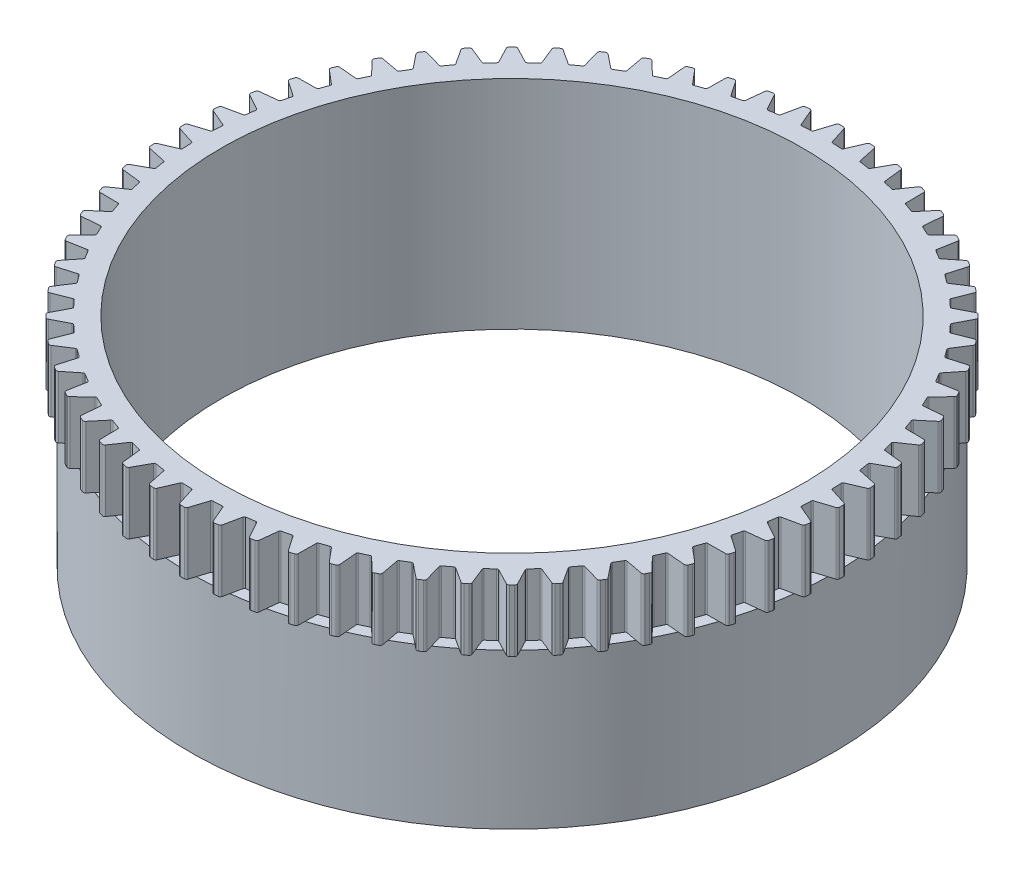
SolidWorks part; units mm, degrees
material "PET"
ref_plane "Front Plane" through (0, 0, 0) normal (0, 0, 1) x (1, 0, 0)
ref_plane "Top Plane" through (0, 0, 0) normal (0, 1, 0) x (1, 0, 0)
ref_plane "Right Plane" through (0, 0, 0) normal (1, 0, 0) x (0, 0, -1)
sketch "Sketch1" plane through (0, 0, 0) normal (0, 1, 0) x (1, 0, 0)
  line L0 (0, 53.7167) -> (0, -50.4595) construction
  line L1 (-0.5164, 42.2908) -> (-1.2072, 40.1152)
  line L2 (-0.2305, 42.5) -> (0.2305, 42.5)
  line L3 (0.5164, 42.2908) -> (1.2072, 40.1152)
  line L4 (3.6313, 42.1378) -> (2.7306, 40.0403)
  line L5 (4.6592, 42.0365) -> (5.1334, 39.8037)
  line L6 (3.9363, 42.3179) -> (4.3951, 42.2728)
  line L7 (7.744, 41.5789) -> (6.642, 39.5799)
  line L8 (8.757, 41.3774) -> (9.0101, 39.1088)
  line L9 (8.0653, 41.7283) -> (8.5174, 41.6384)
  line L10 (11.7822, 40.6197) -> (10.4896, 38.7383)
  line L11 (12.7706, 40.3199) -> (12.8001, 38.0374)
  line L12 (12.1165, 40.7369) -> (12.5577, 40.6031)
  line L13 (15.7069, 39.2692) -> (14.2361, 37.5236)
  line L14 (16.6611, 38.874) -> (16.4667, 36.5996)
  line L15 (16.0511, 39.3531) -> (16.477, 39.1767)
  line L16 (19.4803, 37.5406) -> (17.8455, 35.9475)
  line L17 (20.3912, 37.0537) -> (19.9748, 34.8093)
  line L18 (19.8311, 37.5903) -> (20.2376, 37.373)
  line L19 (23.0661, 35.4504) -> (21.283, 34.0252)
  line L20 (23.9249, 34.8766) -> (23.2906, 32.6838)
  line L21 (23.4201, 35.4655) -> (23.8034, 35.2094)
  line L22 (26.4298, 33.0188) -> (24.5156, 31.7753)
  line L23 (27.2282, 32.3636) -> (26.382, 30.2436)
  line L24 (26.7835, 32.9992) -> (27.1399, 32.7067)
  line L25 (29.5389, 30.2693) -> (27.5121, 29.2193)
  line L26 (30.2693, 29.5389) -> (29.2193, 27.5121)
  line L27 (29.8891, 30.215) -> (30.215, 29.8891)
  line L28 (32.3636, 27.2282) -> (30.2436, 26.382)
  line L29 (33.0188, 26.4298) -> (31.7753, 24.5156)
  line L30 (32.7067, 27.1399) -> (32.9992, 26.7835)
  line L31 (34.8766, 23.9249) -> (32.6838, 23.2906)
  line L32 (35.4504, 23.0661) -> (34.0252, 21.283)
  line L33 (35.2094, 23.8034) -> (35.4655, 23.4201)
  line L34 (37.0537, 20.3912) -> (34.8093, 19.9748)
  line L35 (37.5406, 19.4803) -> (35.9475, 17.8455)
  line L36 (37.373, 20.2376) -> (37.5903, 19.8311)
  line L37 (38.874, 16.6611) -> (36.5996, 16.4667)
  line L38 (39.2692, 15.7069) -> (37.5236, 14.2361)
  line L39 (39.1767, 16.477) -> (39.3531, 16.0511)
  line L40 (40.3199, 12.7706) -> (38.0374, 12.8001)
  line L41 (40.6197, 11.7822) -> (38.7383, 10.4896)
  line L42 (40.6031, 12.5577) -> (40.7369, 12.1165)
  line L43 (41.3774, 8.757) -> (39.1088, 9.0101)
  line L44 (41.5789, 7.744) -> (39.5799, 6.642)
  line L45 (41.6384, 8.5174) -> (41.7283, 8.0653)
  line L46 (42.0365, 4.6592) -> (39.8037, 5.1334)
  line L47 (42.1378, 3.6313) -> (40.0403, 2.7306)
  line L48 (42.2728, 4.3951) -> (42.3179, 3.9363)
  line L49 (42.2908, 0.5164) -> (40.1152, 1.2072)
  line L50 (42.2908, -0.5164) -> (40.1152, -1.2072)
  line L51 (42.5, 0.2305) -> (42.5, -0.2305)
  line L52 (42.1378, -3.6313) -> (40.0403, -2.7306)
  line L53 (42.0365, -4.6592) -> (39.8037, -5.1334)
  line L54 (42.3179, -3.9363) -> (42.2728, -4.3951)
  line L55 (41.5789, -7.744) -> (39.5799, -6.642)
  line L56 (41.3774, -8.757) -> (39.1088, -9.0101)
  line L57 (41.7283, -8.0653) -> (41.6384, -8.5174)
  line L58 (40.6197, -11.7822) -> (38.7383, -10.4896)
  line L59 (40.3199, -12.7706) -> (38.0374, -12.8001)
  line L60 (40.7369, -12.1165) -> (40.6031, -12.5577)
  line L61 (39.2692, -15.7069) -> (37.5236, -14.2361)
  line L62 (38.874, -16.6611) -> (36.5996, -16.4667)
  line L63 (39.3531, -16.0511) -> (39.1767, -16.477)
  line L64 (37.5406, -19.4803) -> (35.9475, -17.8455)
  line L65 (37.0537, -20.3912) -> (34.8093, -19.9748)
  line L66 (37.5903, -19.8311) -> (37.373, -20.2376)
  line L67 (35.4504, -23.0661) -> (34.0252, -21.283)
  line L68 (34.8766, -23.9249) -> (32.6838, -23.2906)
  line L69 (35.4655, -23.4201) -> (35.2094, -23.8034)
  line L70 (33.0188, -26.4298) -> (31.7753, -24.5156)
  line L71 (32.3636, -27.2282) -> (30.2436, -26.382)
  line L72 (32.9992, -26.7835) -> (32.7067, -27.1399)
  line L73 (30.2693, -29.5389) -> (29.2193, -27.5121)
  line L74 (29.5389, -30.2693) -> (27.5121, -29.2193)
  line L75 (30.215, -29.8891) -> (29.8891, -30.215)
  line L76 (27.2282, -32.3636) -> (26.382, -30.2436)
  line L77 (26.4298, -33.0188) -> (24.5156, -31.7753)
  line L78 (27.1399, -32.7067) -> (26.7835, -32.9992)
  line L79 (23.9249, -34.8766) -> (23.2906, -32.6838)
  line L80 (23.0661, -35.4504) -> (21.283, -34.0252)
  line L81 (23.8034, -35.2094) -> (23.4201, -35.4655)
  line L82 (20.3912, -37.0537) -> (19.9748, -34.8093)
  line L83 (19.4803, -37.5406) -> (17.8455, -35.9475)
  line L84 (20.2376, -37.373) -> (19.8311, -37.5903)
  line L85 (16.6611, -38.874) -> (16.4667, -36.5996)
  line L86 (15.7069, -39.2692) -> (14.2361, -37.5236)
  line L87 (16.477, -39.1767) -> (16.0511, -39.3531)
  line L88 (12.7706, -40.3199) -> (12.8001, -38.0374)
  line L89 (11.7822, -40.6197) -> (10.4896, -38.7383)
  line L90 (12.5577, -40.6031) -> (12.1165, -40.7369)
  line L91 (8.757, -41.3774) -> (9.0101, -39.1088)
  line L92 (7.744, -41.5789) -> (6.642, -39.5799)
  line L93 (8.5174, -41.6384) -> (8.0653, -41.7283)
  line L94 (4.6592, -42.0365) -> (5.1334, -39.8037)
  line L95 (3.6313, -42.1378) -> (2.7306, -40.0403)
  line L96 (4.3951, -42.2728) -> (3.9363, -42.3179)
  line L97 (0.5164, -42.2908) -> (1.2072, -40.1152)
  line L98 (-0.5164, -42.2908) -> (-1.2072, -40.1152)
  line L99 (0.2305, -42.5) -> (-0.2305, -42.5)
  line L100 (-3.6313, -42.1378) -> (-2.7306, -40.0403)
  line L101 (-4.6592, -42.0365) -> (-5.1334, -39.8037)
  line L102 (-3.9363, -42.3179) -> (-4.3951, -42.2728)
  line L103 (-7.744, -41.5789) -> (-6.642, -39.5799)
  line L104 (-8.757, -41.3774) -> (-9.0101, -39.1088)
  line L105 (-8.0653, -41.7283) -> (-8.5174, -41.6384)
  line L106 (-11.7822, -40.6197) -> (-10.4896, -38.7383)
  line L107 (-12.7706, -40.3199) -> (-12.8001, -38.0374)
  line L108 (-12.1165, -40.7369) -> (-12.5577, -40.6031)
  line L109 (-15.7069, -39.2692) -> (-14.2361, -37.5236)
  line L110 (-16.6611, -38.874) -> (-16.4667, -36.5996)
  line L111 (-16.0511, -39.3531) -> (-16.477, -39.1767)
  line L112 (-19.4803, -37.5406) -> (-17.8455, -35.9475)
  line L113 (-20.3912, -37.0537) -> (-19.9748, -34.8093)
  line L114 (-19.8311, -37.5903) -> (-20.2376, -37.373)
  line L115 (-23.0661, -35.4504) -> (-21.283, -34.0252)
  line L116 (-23.9249, -34.8766) -> (-23.2906, -32.6838)
  line L117 (-23.4201, -35.4655) -> (-23.8034, -35.2094)
  line L118 (-26.4298, -33.0188) -> (-24.5156, -31.7753)
  line L119 (-27.2282, -32.3636) -> (-26.382, -30.2436)
  line L120 (-26.7835, -32.9992) -> (-27.1399, -32.7067)
  line L121 (-29.5389, -30.2693) -> (-27.5121, -29.2193)
  line L122 (-30.2693, -29.5389) -> (-29.2193, -27.5121)
  line L123 (-29.8891, -30.215) -> (-30.215, -29.8891)
  line L124 (-32.3636, -27.2282) -> (-30.2436, -26.382)
  line L125 (-33.0188, -26.4298) -> (-31.7753, -24.5156)
  line L126 (-32.7067, -27.1399) -> (-32.9992, -26.7835)
  line L127 (-34.8766, -23.9249) -> (-32.6838, -23.2906)
  line L128 (-35.4504, -23.0661) -> (-34.0252, -21.283)
  line L129 (-35.2094, -23.8034) -> (-35.4655, -23.4201)
  line L130 (-37.0537, -20.3912) -> (-34.8093, -19.9748)
  line L131 (-37.5406, -19.4803) -> (-35.9475, -17.8455)
  line L132 (-37.373, -20.2376) -> (-37.5903, -19.8311)
  line L133 (-38.874, -16.6611) -> (-36.5996, -16.4667)
  line L134 (-39.2692, -15.7069) -> (-37.5236, -14.2361)
  line L135 (-39.1767, -16.477) -> (-39.3531, -16.0511)
  line L136 (-40.3199, -12.7706) -> (-38.0374, -12.8001)
  line L137 (-40.6197, -11.7822) -> (-38.7383, -10.4896)
  line L138 (-40.6031, -12.5577) -> (-40.7369, -12.1165)
  line L139 (-41.3774, -8.757) -> (-39.1088, -9.0101)
  line L140 (-41.5789, -7.744) -> (-39.5799, -6.642)
  line L141 (-41.6384, -8.5174) -> (-41.7283, -8.0653)
  line L142 (-42.0365, -4.6592) -> (-39.8037, -5.1334)
  line L143 (-42.1378, -3.6313) -> (-40.0403, -2.7306)
  line L144 (-42.2728, -4.3951) -> (-42.3179, -3.9363)
  line L145 (-42.2908, -0.5164) -> (-40.1152, -1.2072)
  line L146 (-42.2908, 0.5164) -> (-40.1152, 1.2072)
  line L147 (-42.5, -0.2305) -> (-42.5, 0.2305)
  line L148 (-42.1378, 3.6313) -> (-40.0403, 2.7306)
  line L149 (-42.0365, 4.6592) -> (-39.8037, 5.1334)
  line L150 (-42.3179, 3.9363) -> (-42.2728, 4.3951)
  line L151 (-41.5789, 7.744) -> (-39.5799, 6.642)
  line L152 (-41.3774, 8.757) -> (-39.1088, 9.0101)
  line L153 (-41.7283, 8.0653) -> (-41.6384, 8.5174)
  line L154 (-40.6197, 11.7822) -> (-38.7383, 10.4896)
  line L155 (-40.3199, 12.7706) -> (-38.0374, 12.8001)
  line L156 (-40.7369, 12.1165) -> (-40.6031, 12.5577)
  line L157 (-39.2692, 15.7069) -> (-37.5236, 14.2361)
  line L158 (-38.874, 16.6611) -> (-36.5996, 16.4667)
  line L159 (-39.3531, 16.0511) -> (-39.1767, 16.477)
  line L160 (-37.5406, 19.4803) -> (-35.9475, 17.8455)
  line L161 (-37.0537, 20.3912) -> (-34.8093, 19.9748)
  line L162 (-37.5903, 19.8311) -> (-37.373, 20.2376)
  line L163 (-35.4504, 23.0661) -> (-34.0252, 21.283)
  line L164 (-34.8766, 23.9249) -> (-32.6838, 23.2906)
  line L165 (-35.4655, 23.4201) -> (-35.2094, 23.8034)
  line L166 (-33.0188, 26.4298) -> (-31.7753, 24.5156)
  line L167 (-32.3636, 27.2282) -> (-30.2436, 26.382)
  line L168 (-32.9992, 26.7835) -> (-32.7067, 27.1399)
  line L169 (-30.2693, 29.5389) -> (-29.2193, 27.5121)
  line L170 (-29.5389, 30.2693) -> (-27.5121, 29.2193)
  line L171 (-30.215, 29.8891) -> (-29.8891, 30.215)
  line L172 (-27.2282, 32.3636) -> (-26.382, 30.2436)
  line L173 (-26.4298, 33.0188) -> (-24.5156, 31.7753)
  line L174 (-27.1399, 32.7067) -> (-26.7835, 32.9992)
  line L175 (-23.9249, 34.8766) -> (-23.2906, 32.6838)
  line L176 (-23.0661, 35.4504) -> (-21.283, 34.0252)
  line L177 (-23.8034, 35.2094) -> (-23.4201, 35.4655)
  line L178 (-20.3912, 37.0537) -> (-19.9748, 34.8093)
  line L179 (-19.4803, 37.5406) -> (-17.8455, 35.9475)
  line L180 (-20.2376, 37.373) -> (-19.8311, 37.5903)
  line L181 (-16.6611, 38.874) -> (-16.4667, 36.5996)
  line L182 (-15.7069, 39.2692) -> (-14.2361, 37.5236)
  line L183 (-16.477, 39.1767) -> (-16.0511, 39.3531)
  line L184 (-12.7706, 40.3199) -> (-12.8001, 38.0374)
  line L185 (-11.7822, 40.6197) -> (-10.4896, 38.7383)
  line L186 (-12.5577, 40.6031) -> (-12.1165, 40.7369)
  line L187 (-8.757, 41.3774) -> (-9.0101, 39.1088)
  line L188 (-7.744, 41.5789) -> (-6.642, 39.5799)
  line L189 (-8.5174, 41.6384) -> (-8.0653, 41.7283)
  line L190 (-4.6592, 42.0365) -> (-5.1334, 39.8037)
  line L191 (-3.6313, 42.1378) -> (-2.7306, 40.0403)
  line L192 (-4.3951, 42.2728) -> (-3.9363, 42.3179)
  arc A0 (-1.3909, 39.9758) -> (-2.5341, 39.9196) centre (0, 0) ccw
  arc A1 (-0.5164, 42.2908) -> (-0.2305, 42.5) centre (-0.2305, 42.2) cw
  arc A2 (0.2305, 42.5) -> (0.5164, 42.2908) centre (0.2305, 42.2) cw
  arc A3 (1.2072, 40.1152) -> (1.3909, 39.9758) centre (1.3979, 40.1757) ccw
  arc A4 (-1.2072, 40.1152) -> (-1.3909, 39.9758) centre (-1.3979, 40.1757) cw
  arc A5 (2.7306, 40.0403) -> (2.5341, 39.9196) centre (2.5468, 40.1192) cw
  arc A6 (5.1334, 39.8037) -> (5.3025, 39.647) centre (5.329, 39.8452) ccw
  arc A7 (4.3951, 42.2728) -> (4.6592, 42.0365) centre (4.3657, 41.9742) cw
  arc A8 (3.6313, 42.1378) -> (3.9363, 42.3179) centre (3.9069, 42.0194) cw
  arc A9 (6.642, 39.5799) -> (6.4347, 39.479) centre (6.4669, 39.6764) cw
  arc A10 (9.0101, 39.1088) -> (9.1631, 38.9363) centre (9.2089, 39.131) ccw
  arc A11 (8.5174, 41.6384) -> (8.757, 41.3774) centre (8.4589, 41.3442) cw
  arc A12 (7.744, 41.5789) -> (8.0653, 41.7283) centre (8.0067, 41.4341) cw
  arc A13 (10.4896, 38.7383) -> (10.2734, 38.6582) centre (10.3247, 38.8515) cw
  arc A14 (12.8001, 38.0374) -> (12.9354, 37.8507) centre (13, 38.04) ccw
  arc A15 (12.5577, 40.6031) -> (12.7706, 40.3199) centre (12.4706, 40.316) cw
  arc A16 (11.7822, 40.6197) -> (12.1165, 40.7369) centre (12.0294, 40.4498) cw
  arc A17 (14.2361, 37.5236) -> (14.0131, 37.4651) centre (14.0831, 37.6524) cw
  arc A18 (16.4667, 36.5996) -> (16.5831, 36.4006) centre (16.666, 36.5826) ccw
  arc A19 (16.477, 39.1767) -> (16.6611, 38.874) centre (16.3622, 38.8995) cw
  arc A20 (15.7069, 39.2692) -> (16.0511, 39.3531) centre (15.9363, 39.0759) cw
  arc A21 (17.8455, 35.9475) -> (17.6178, 35.9112) centre (17.7059, 36.0907) cw
  arc A22 (19.9748, 34.8093) -> (20.0711, 34.5999) centre (20.1715, 34.7729) ccw
  arc A23 (20.2376, 37.373) -> (20.3912, 37.0537) centre (20.0962, 37.1084) cw
  arc A24 (19.4803, 37.5406) -> (19.8311, 37.5903) centre (19.6897, 37.3257) cw
  arc A25 (21.283, 34.0252) -> (21.0529, 34.0114) centre (21.1581, 34.1815) cw
  arc A26 (23.2906, 32.6838) -> (23.3659, 32.4659) centre (23.4827, 32.6283) ccw
  arc A27 (23.8034, 35.2094) -> (23.9249, 34.8766) centre (23.6367, 34.96) cw
  arc A28 (23.0661, 35.4504) -> (23.4201, 35.4655) centre (23.2534, 35.2161) cw
  arc A29 (24.5156, 31.7753) -> (24.2852, 31.7841) centre (24.4066, 31.943) cw
  arc A30 (26.382, 30.2436) -> (26.4356, 30.0193) centre (26.5677, 30.1694) ccw
  arc A31 (27.1399, 32.7067) -> (27.2282, 32.3636) centre (26.9496, 32.4748) cw
  arc A32 (26.4298, 33.0188) -> (26.7835, 32.9992) centre (26.5932, 32.7673) cw
  arc A33 (27.5121, 29.2193) -> (27.2837, 29.2507) centre (27.4201, 29.3969) cw
  arc A34 (29.2193, 27.5121) -> (29.2507, 27.2837) centre (29.3969, 27.4201) ccw
  arc A35 (30.215, 29.8891) -> (30.2693, 29.5389) centre (30.0029, 29.6769) cw
  arc A36 (29.5389, 30.2693) -> (29.8891, 30.215) centre (29.6769, 30.0029) cw
  arc A37 (30.2436, 26.382) -> (30.0193, 26.4356) centre (30.1694, 26.5677) cw
  arc A38 (31.7753, 24.5156) -> (31.7841, 24.2852) centre (31.943, 24.4066) ccw
  arc A39 (32.9992, 26.7835) -> (33.0188, 26.4298) centre (32.7673, 26.5932) cw
  arc A40 (32.3636, 27.2282) -> (32.7067, 27.1399) centre (32.4748, 26.9496) cw
  arc A41 (32.6838, 23.2906) -> (32.4659, 23.3659) centre (32.6283, 23.4827) cw
  arc A42 (34.0252, 21.283) -> (34.0114, 21.0529) centre (34.1815, 21.1581) ccw
  arc A43 (35.4655, 23.4201) -> (35.4504, 23.0661) centre (35.2161, 23.2534) cw
  arc A44 (34.8766, 23.9249) -> (35.2094, 23.8034) centre (34.96, 23.6367) cw
  arc A45 (34.8093, 19.9748) -> (34.5999, 20.0711) centre (34.7729, 20.1715) cw
  arc A46 (35.9475, 17.8455) -> (35.9112, 17.6178) centre (36.0907, 17.7059) ccw
  arc A47 (37.5903, 19.8311) -> (37.5406, 19.4803) centre (37.3257, 19.6897) cw
  arc A48 (37.0537, 20.3912) -> (37.373, 20.2376) centre (37.1084, 20.0962) cw
  arc A49 (36.5996, 16.4667) -> (36.4006, 16.5831) centre (36.5826, 16.666) cw
  arc A50 (37.5236, 14.2361) -> (37.4651, 14.0131) centre (37.6524, 14.0831) ccw
  arc A51 (39.3531, 16.0511) -> (39.2692, 15.7069) centre (39.0759, 15.9363) cw
  arc A52 (38.874, 16.6611) -> (39.1767, 16.477) centre (38.8995, 16.3622) cw
  arc A53 (38.0374, 12.8001) -> (37.8507, 12.9354) centre (38.04, 13) cw
  arc A54 (38.7383, 10.4896) -> (38.6582, 10.2734) centre (38.8515, 10.3247) ccw
  arc A55 (40.7369, 12.1165) -> (40.6197, 11.7822) centre (40.4498, 12.0294) cw
  arc A56 (40.3199, 12.7706) -> (40.6031, 12.5577) centre (40.316, 12.4706) cw
  arc A57 (39.1088, 9.0101) -> (38.9363, 9.1631) centre (39.131, 9.2089) cw
  arc A58 (39.5799, 6.642) -> (39.479, 6.4347) centre (39.6764, 6.4669) ccw
  arc A59 (41.7283, 8.0653) -> (41.5789, 7.744) centre (41.4341, 8.0067) cw
  arc A60 (41.3774, 8.757) -> (41.6384, 8.5174) centre (41.3442, 8.4589) cw
  arc A61 (39.8037, 5.1334) -> (39.647, 5.3025) centre (39.8452, 5.329) cw
  arc A62 (40.0403, 2.7306) -> (39.9196, 2.5341) centre (40.1192, 2.5468) ccw
  arc A63 (42.3179, 3.9363) -> (42.1378, 3.6313) centre (42.0194, 3.9069) cw
  arc A64 (42.0365, 4.6592) -> (42.2728, 4.3951) centre (41.9742, 4.3657) cw
  arc A65 (40.1152, 1.2072) -> (39.9758, 1.3909) centre (40.1757, 1.3979) cw
  arc A66 (40.1152, -1.2072) -> (39.9758, -1.3909) centre (40.1757, -1.3979) ccw
  arc A67 (42.5, -0.2305) -> (42.2908, -0.5164) centre (42.2, -0.2305) cw
  arc A68 (42.2908, 0.5164) -> (42.5, 0.2305) centre (42.2, 0.2305) cw
  arc A69 (40.0403, -2.7306) -> (39.9196, -2.5341) centre (40.1192, -2.5468) cw
  arc A70 (39.8037, -5.1334) -> (39.647, -5.3025) centre (39.8452, -5.329) ccw
  arc A71 (42.2728, -4.3951) -> (42.0365, -4.6592) centre (41.9742, -4.3657) cw
  arc A72 (42.1378, -3.6313) -> (42.3179, -3.9363) centre (42.0194, -3.9069) cw
  arc A73 (39.5799, -6.642) -> (39.479, -6.4347) centre (39.6764, -6.4669) cw
  arc A74 (39.1088, -9.0101) -> (38.9363, -9.1631) centre (39.131, -9.2089) ccw
  arc A75 (41.6384, -8.5174) -> (41.3774, -8.757) centre (41.3442, -8.4589) cw
  arc A76 (41.5789, -7.744) -> (41.7283, -8.0653) centre (41.4341, -8.0067) cw
  arc A77 (38.7383, -10.4896) -> (38.6582, -10.2734) centre (38.8515, -10.3247) cw
  arc A78 (38.0374, -12.8001) -> (37.8507, -12.9354) centre (38.04, -13) ccw
  arc A79 (40.6031, -12.5577) -> (40.3199, -12.7706) centre (40.316, -12.4706) cw
  arc A80 (40.6197, -11.7822) -> (40.7369, -12.1165) centre (40.4498, -12.0294) cw
  arc A81 (37.5236, -14.2361) -> (37.4651, -14.0131) centre (37.6524, -14.0831) cw
  arc A82 (36.5996, -16.4667) -> (36.4006, -16.5831) centre (36.5826, -16.666) ccw
  arc A83 (39.1767, -16.477) -> (38.874, -16.6611) centre (38.8995, -16.3622) cw
  arc A84 (39.2692, -15.7069) -> (39.3531, -16.0511) centre (39.0759, -15.9363) cw
  arc A85 (35.9475, -17.8455) -> (35.9112, -17.6178) centre (36.0907, -17.7059) cw
  arc A86 (34.8093, -19.9748) -> (34.5999, -20.0711) centre (34.7729, -20.1715) ccw
  arc A87 (37.373, -20.2376) -> (37.0537, -20.3912) centre (37.1084, -20.0962) cw
  arc A88 (37.5406, -19.4803) -> (37.5903, -19.8311) centre (37.3257, -19.6897) cw
  arc A89 (34.0252, -21.283) -> (34.0114, -21.0529) centre (34.1815, -21.1581) cw
  arc A90 (32.6838, -23.2906) -> (32.4659, -23.3659) centre (32.6283, -23.4827) ccw
  arc A91 (35.2094, -23.8034) -> (34.8766, -23.9249) centre (34.96, -23.6367) cw
  arc A92 (35.4504, -23.0661) -> (35.4655, -23.4201) centre (35.2161, -23.2534) cw
  arc A93 (31.7753, -24.5156) -> (31.7841, -24.2852) centre (31.943, -24.4066) cw
  arc A94 (30.2436, -26.382) -> (30.0193, -26.4356) centre (30.1694, -26.5677) ccw
  arc A95 (32.7067, -27.1399) -> (32.3636, -27.2282) centre (32.4748, -26.9496) cw
  arc A96 (33.0188, -26.4298) -> (32.9992, -26.7835) centre (32.7673, -26.5932) cw
  arc A97 (29.2193, -27.5121) -> (29.2507, -27.2837) centre (29.3969, -27.4201) cw
  arc A98 (27.5121, -29.2193) -> (27.2837, -29.2507) centre (27.4201, -29.3969) ccw
  arc A99 (29.8891, -30.215) -> (29.5389, -30.2693) centre (29.6769, -30.0029) cw
  arc A100 (30.2693, -29.5389) -> (30.215, -29.8891) centre (30.0029, -29.6769) cw
  arc A101 (26.382, -30.2436) -> (26.4356, -30.0193) centre (26.5677, -30.1694) cw
  arc A102 (24.5156, -31.7753) -> (24.2852, -31.7841) centre (24.4066, -31.943) ccw
  arc A103 (26.7835, -32.9992) -> (26.4298, -33.0188) centre (26.5932, -32.7673) cw
  arc A104 (27.2282, -32.3636) -> (27.1399, -32.7067) centre (26.9496, -32.4748) cw
  arc A105 (23.2906, -32.6838) -> (23.3659, -32.4659) centre (23.4827, -32.6283) cw
  arc A106 (21.283, -34.0252) -> (21.0529, -34.0114) centre (21.1581, -34.1815) ccw
  arc A107 (23.4201, -35.4655) -> (23.0661, -35.4504) centre (23.2534, -35.2161) cw
  arc A108 (23.9249, -34.8766) -> (23.8034, -35.2094) centre (23.6367, -34.96) cw
  arc A109 (19.9748, -34.8093) -> (20.0711, -34.5999) centre (20.1715, -34.7729) cw
  arc A110 (17.8455, -35.9475) -> (17.6178, -35.9112) centre (17.7059, -36.0907) ccw
  arc A111 (19.8311, -37.5903) -> (19.4803, -37.5406) centre (19.6897, -37.3257) cw
  arc A112 (20.3912, -37.0537) -> (20.2376, -37.373) centre (20.0962, -37.1084) cw
  arc A113 (16.4667, -36.5996) -> (16.5831, -36.4006) centre (16.666, -36.5826) cw
  arc A114 (14.2361, -37.5236) -> (14.0131, -37.4651) centre (14.0831, -37.6524) ccw
  arc A115 (16.0511, -39.3531) -> (15.7069, -39.2692) centre (15.9363, -39.0759) cw
  arc A116 (16.6611, -38.874) -> (16.477, -39.1767) centre (16.3622, -38.8995) cw
  arc A117 (12.8001, -38.0374) -> (12.9354, -37.8507) centre (13, -38.04) cw
  arc A118 (10.4896, -38.7383) -> (10.2734, -38.6582) centre (10.3247, -38.8515) ccw
  arc A119 (12.1165, -40.7369) -> (11.7822, -40.6197) centre (12.0294, -40.4498) cw
  arc A120 (12.7706, -40.3199) -> (12.5577, -40.6031) centre (12.4706, -40.316) cw
  arc A121 (9.0101, -39.1088) -> (9.1631, -38.9363) centre (9.2089, -39.131) cw
  arc A122 (6.642, -39.5799) -> (6.4347, -39.479) centre (6.4669, -39.6764) ccw
  arc A123 (8.0653, -41.7283) -> (7.744, -41.5789) centre (8.0067, -41.4341) cw
  arc A124 (8.757, -41.3774) -> (8.5174, -41.6384) centre (8.4589, -41.3442) cw
  arc A125 (5.1334, -39.8037) -> (5.3025, -39.647) centre (5.329, -39.8452) cw
  arc A126 (2.7306, -40.0403) -> (2.5341, -39.9196) centre (2.5468, -40.1192) ccw
  arc A127 (3.9363, -42.3179) -> (3.6313, -42.1378) centre (3.9069, -42.0194) cw
  arc A128 (4.6592, -42.0365) -> (4.3951, -42.2728) centre (4.3657, -41.9742) cw
  arc A129 (1.2072, -40.1152) -> (1.3909, -39.9758) centre (1.3979, -40.1757) cw
  arc A130 (-1.2072, -40.1152) -> (-1.3909, -39.9758) centre (-1.3979, -40.1757) ccw
  arc A131 (-0.2305, -42.5) -> (-0.5164, -42.2908) centre (-0.2305, -42.2) cw
  arc A132 (0.5164, -42.2908) -> (0.2305, -42.5) centre (0.2305, -42.2) cw
  arc A133 (-2.7306, -40.0403) -> (-2.5341, -39.9196) centre (-2.5468, -40.1192) cw
  arc A134 (-5.1334, -39.8037) -> (-5.3025, -39.647) centre (-5.329, -39.8452) ccw
  arc A135 (-4.3951, -42.2728) -> (-4.6592, -42.0365) centre (-4.3657, -41.9742) cw
  arc A136 (-3.6313, -42.1378) -> (-3.9363, -42.3179) centre (-3.9069, -42.0194) cw
  arc A137 (-6.642, -39.5799) -> (-6.4347, -39.479) centre (-6.4669, -39.6764) cw
  arc A138 (-9.0101, -39.1088) -> (-9.1631, -38.9363) centre (-9.2089, -39.131) ccw
  arc A139 (-8.5174, -41.6384) -> (-8.757, -41.3774) centre (-8.4589, -41.3442) cw
  arc A140 (-7.744, -41.5789) -> (-8.0653, -41.7283) centre (-8.0067, -41.4341) cw
  arc A141 (-10.4896, -38.7383) -> (-10.2734, -38.6582) centre (-10.3247, -38.8515) cw
  arc A142 (-12.8001, -38.0374) -> (-12.9354, -37.8507) centre (-13, -38.04) ccw
  arc A143 (-12.5577, -40.6031) -> (-12.7706, -40.3199) centre (-12.4706, -40.316) cw
  arc A144 (-11.7822, -40.6197) -> (-12.1165, -40.7369) centre (-12.0294, -40.4498) cw
  arc A145 (-14.2361, -37.5236) -> (-14.0131, -37.4651) centre (-14.0831, -37.6524) cw
  arc A146 (-16.4667, -36.5996) -> (-16.5831, -36.4006) centre (-16.666, -36.5826) ccw
  arc A147 (-16.477, -39.1767) -> (-16.6611, -38.874) centre (-16.3622, -38.8995) cw
  arc A148 (-15.7069, -39.2692) -> (-16.0511, -39.3531) centre (-15.9363, -39.0759) cw
  arc A149 (-17.8455, -35.9475) -> (-17.6178, -35.9112) centre (-17.7059, -36.0907) cw
  arc A150 (-19.9748, -34.8093) -> (-20.0711, -34.5999) centre (-20.1715, -34.7729) ccw
  arc A151 (-20.2376, -37.373) -> (-20.3912, -37.0537) centre (-20.0962, -37.1084) cw
  arc A152 (-19.4803, -37.5406) -> (-19.8311, -37.5903) centre (-19.6897, -37.3257) cw
  arc A153 (-21.283, -34.0252) -> (-21.0529, -34.0114) centre (-21.1581, -34.1815) cw
  arc A154 (-23.2906, -32.6838) -> (-23.3659, -32.4659) centre (-23.4827, -32.6283) ccw
  arc A155 (-23.8034, -35.2094) -> (-23.9249, -34.8766) centre (-23.6367, -34.96) cw
  arc A156 (-23.0661, -35.4504) -> (-23.4201, -35.4655) centre (-23.2534, -35.2161) cw
  arc A157 (-24.5156, -31.7753) -> (-24.2852, -31.7841) centre (-24.4066, -31.943) cw
  arc A158 (-26.382, -30.2436) -> (-26.4356, -30.0193) centre (-26.5677, -30.1694) ccw
  arc A159 (-27.1399, -32.7067) -> (-27.2282, -32.3636) centre (-26.9496, -32.4748) cw
  arc A160 (-26.4298, -33.0188) -> (-26.7835, -32.9992) centre (-26.5932, -32.7673) cw
  arc A161 (-27.5121, -29.2193) -> (-27.2837, -29.2507) centre (-27.4201, -29.3969) cw
  arc A162 (-29.2193, -27.5121) -> (-29.2507, -27.2837) centre (-29.3969, -27.4201) ccw
  arc A163 (-30.215, -29.8891) -> (-30.2693, -29.5389) centre (-30.0029, -29.6769) cw
  arc A164 (-29.5389, -30.2693) -> (-29.8891, -30.215) centre (-29.6769, -30.0029) cw
  arc A165 (-30.2436, -26.382) -> (-30.0193, -26.4356) centre (-30.1694, -26.5677) cw
  arc A166 (-31.7753, -24.5156) -> (-31.7841, -24.2852) centre (-31.943, -24.4066) ccw
  arc A167 (-32.9992, -26.7835) -> (-33.0188, -26.4298) centre (-32.7673, -26.5932) cw
  arc A168 (-32.3636, -27.2282) -> (-32.7067, -27.1399) centre (-32.4748, -26.9496) cw
  arc A169 (-32.6838, -23.2906) -> (-32.4659, -23.3659) centre (-32.6283, -23.4827) cw
  arc A170 (-34.0252, -21.283) -> (-34.0114, -21.0529) centre (-34.1815, -21.1581) ccw
  arc A171 (-35.4655, -23.4201) -> (-35.4504, -23.0661) centre (-35.2161, -23.2534) cw
  arc A172 (-34.8766, -23.9249) -> (-35.2094, -23.8034) centre (-34.96, -23.6367) cw
  arc A173 (-34.8093, -19.9748) -> (-34.5999, -20.0711) centre (-34.7729, -20.1715) cw
  arc A174 (-35.9475, -17.8455) -> (-35.9112, -17.6178) centre (-36.0907, -17.7059) ccw
  arc A175 (-37.5903, -19.8311) -> (-37.5406, -19.4803) centre (-37.3257, -19.6897) cw
  arc A176 (-37.0537, -20.3912) -> (-37.373, -20.2376) centre (-37.1084, -20.0962) cw
  arc A177 (-36.5996, -16.4667) -> (-36.4006, -16.5831) centre (-36.5826, -16.666) cw
  arc A178 (-37.5236, -14.2361) -> (-37.4651, -14.0131) centre (-37.6524, -14.0831) ccw
  arc A179 (-39.3531, -16.0511) -> (-39.2692, -15.7069) centre (-39.0759, -15.9363) cw
  arc A180 (-38.874, -16.6611) -> (-39.1767, -16.477) centre (-38.8995, -16.3622) cw
  arc A181 (-38.0374, -12.8001) -> (-37.8507, -12.9354) centre (-38.04, -13) cw
  arc A182 (-38.7383, -10.4896) -> (-38.6582, -10.2734) centre (-38.8515, -10.3247) ccw
  arc A183 (-40.7369, -12.1165) -> (-40.6197, -11.7822) centre (-40.4498, -12.0294) cw
  arc A184 (-40.3199, -12.7706) -> (-40.6031, -12.5577) centre (-40.316, -12.4706) cw
  arc A185 (-39.1088, -9.0101) -> (-38.9363, -9.1631) centre (-39.131, -9.2089) cw
  arc A186 (-39.5799, -6.642) -> (-39.479, -6.4347) centre (-39.6764, -6.4669) ccw
  arc A187 (-41.7283, -8.0653) -> (-41.5789, -7.744) centre (-41.4341, -8.0067) cw
  arc A188 (-41.3774, -8.757) -> (-41.6384, -8.5174) centre (-41.3442, -8.4589) cw
  arc A189 (-39.8037, -5.1334) -> (-39.647, -5.3025) centre (-39.8452, -5.329) cw
  arc A190 (-40.0403, -2.7306) -> (-39.9196, -2.5341) centre (-40.1192, -2.5468) ccw
  arc A191 (-42.3179, -3.9363) -> (-42.1378, -3.6313) centre (-42.0194, -3.9069) cw
  arc A192 (-42.0365, -4.6592) -> (-42.2728, -4.3951) centre (-41.9742, -4.3657) cw
  arc A193 (-40.1152, -1.2072) -> (-39.9758, -1.3909) centre (-40.1757, -1.3979) cw
  arc A194 (-40.1152, 1.2072) -> (-39.9758, 1.3909) centre (-40.1757, 1.3979) ccw
  arc A195 (-42.5, 0.2305) -> (-42.2908, 0.5164) centre (-42.2, 0.2305) cw
  arc A196 (-42.2908, -0.5164) -> (-42.5, -0.2305) centre (-42.2, -0.2305) cw
  arc A197 (-40.0403, 2.7306) -> (-39.9196, 2.5341) centre (-40.1192, 2.5468) cw
  arc A198 (-39.8037, 5.1334) -> (-39.647, 5.3025) centre (-39.8452, 5.329) ccw
  arc A199 (-42.2728, 4.3951) -> (-42.0365, 4.6592) centre (-41.9742, 4.3657) cw
  arc A200 (-42.1378, 3.6313) -> (-42.3179, 3.9363) centre (-42.0194, 3.9069) cw
  arc A201 (-39.5799, 6.642) -> (-39.479, 6.4347) centre (-39.6764, 6.4669) cw
  arc A202 (-39.1088, 9.0101) -> (-38.9363, 9.1631) centre (-39.131, 9.2089) ccw
  arc A203 (-41.6384, 8.5174) -> (-41.3774, 8.757) centre (-41.3442, 8.4589) cw
  arc A204 (-41.5789, 7.744) -> (-41.7283, 8.0653) centre (-41.4341, 8.0067) cw
  arc A205 (-38.7383, 10.4896) -> (-38.6582, 10.2734) centre (-38.8515, 10.3247) cw
  arc A206 (-38.0374, 12.8001) -> (-37.8507, 12.9354) centre (-38.04, 13) ccw
  arc A207 (-40.6031, 12.5577) -> (-40.3199, 12.7706) centre (-40.316, 12.4706) cw
  arc A208 (-40.6197, 11.7822) -> (-40.7369, 12.1165) centre (-40.4498, 12.0294) cw
  arc A209 (-37.5236, 14.2361) -> (-37.4651, 14.0131) centre (-37.6524, 14.0831) cw
  arc A210 (-36.5996, 16.4667) -> (-36.4006, 16.5831) centre (-36.5826, 16.666) ccw
  arc A211 (-39.1767, 16.477) -> (-38.874, 16.6611) centre (-38.8995, 16.3622) cw
  arc A212 (-39.2692, 15.7069) -> (-39.3531, 16.0511) centre (-39.0759, 15.9363) cw
  arc A213 (-35.9475, 17.8455) -> (-35.9112, 17.6178) centre (-36.0907, 17.7059) cw
  arc A214 (-34.8093, 19.9748) -> (-34.5999, 20.0711) centre (-34.7729, 20.1715) ccw
  arc A215 (-37.373, 20.2376) -> (-37.0537, 20.3912) centre (-37.1084, 20.0962) cw
  arc A216 (-37.5406, 19.4803) -> (-37.5903, 19.8311) centre (-37.3257, 19.6897) cw
  arc A217 (-34.0252, 21.283) -> (-34.0114, 21.0529) centre (-34.1815, 21.1581) cw
  arc A218 (-32.6838, 23.2906) -> (-32.4659, 23.3659) centre (-32.6283, 23.4827) ccw
  arc A219 (-35.2094, 23.8034) -> (-34.8766, 23.9249) centre (-34.96, 23.6367) cw
  arc A220 (-35.4504, 23.0661) -> (-35.4655, 23.4201) centre (-35.2161, 23.2534) cw
  arc A221 (-31.7753, 24.5156) -> (-31.7841, 24.2852) centre (-31.943, 24.4066) cw
  arc A222 (-30.2436, 26.382) -> (-30.0193, 26.4356) centre (-30.1694, 26.5677) ccw
  arc A223 (-32.7067, 27.1399) -> (-32.3636, 27.2282) centre (-32.4748, 26.9496) cw
  arc A224 (-33.0188, 26.4298) -> (-32.9992, 26.7835) centre (-32.7673, 26.5932) cw
  arc A225 (-29.2193, 27.5121) -> (-29.2507, 27.2837) centre (-29.3969, 27.4201) cw
  arc A226 (-27.5121, 29.2193) -> (-27.2837, 29.2507) centre (-27.4201, 29.3969) ccw
  arc A227 (-29.8891, 30.215) -> (-29.5389, 30.2693) centre (-29.6769, 30.0029) cw
  arc A228 (-30.2693, 29.5389) -> (-30.215, 29.8891) centre (-30.0029, 29.6769) cw
  arc A229 (-26.382, 30.2436) -> (-26.4356, 30.0193) centre (-26.5677, 30.1694) cw
  arc A230 (-24.5156, 31.7753) -> (-24.2852, 31.7841) centre (-24.4066, 31.943) ccw
  arc A231 (-26.7835, 32.9992) -> (-26.4298, 33.0188) centre (-26.5932, 32.7673) cw
  arc A232 (-27.2282, 32.3636) -> (-27.1399, 32.7067) centre (-26.9496, 32.4748) cw
  arc A233 (-23.2906, 32.6838) -> (-23.3659, 32.4659) centre (-23.4827, 32.6283) cw
  arc A234 (-21.283, 34.0252) -> (-21.0529, 34.0114) centre (-21.1581, 34.1815) ccw
  arc A235 (-23.4201, 35.4655) -> (-23.0661, 35.4504) centre (-23.2534, 35.2161) cw
  arc A236 (-23.9249, 34.8766) -> (-23.8034, 35.2094) centre (-23.6367, 34.96) cw
  arc A237 (-19.9748, 34.8093) -> (-20.0711, 34.5999) centre (-20.1715, 34.7729) cw
  arc A238 (-17.8455, 35.9475) -> (-17.6178, 35.9112) centre (-17.7059, 36.0907) ccw
  arc A239 (-19.8311, 37.5903) -> (-19.4803, 37.5406) centre (-19.6897, 37.3257) cw
  arc A240 (-20.3912, 37.0537) -> (-20.2376, 37.373) centre (-20.0962, 37.1084) cw
  arc A241 (-16.4667, 36.5996) -> (-16.5831, 36.4006) centre (-16.666, 36.5826) cw
  arc A242 (-14.2361, 37.5236) -> (-14.0131, 37.4651) centre (-14.0831, 37.6524) ccw
  arc A243 (-16.0511, 39.3531) -> (-15.7069, 39.2692) centre (-15.9363, 39.0759) cw
  arc A244 (-16.6611, 38.874) -> (-16.477, 39.1767) centre (-16.3622, 38.8995) cw
  arc A245 (-12.8001, 38.0374) -> (-12.9354, 37.8507) centre (-13, 38.04) cw
  arc A246 (-10.4896, 38.7383) -> (-10.2734, 38.6582) centre (-10.3247, 38.8515) ccw
  arc A247 (-12.1165, 40.7369) -> (-11.7822, 40.6197) centre (-12.0294, 40.4498) cw
  arc A248 (-12.7706, 40.3199) -> (-12.5577, 40.6031) centre (-12.4706, 40.316) cw
  arc A249 (-9.0101, 39.1088) -> (-9.1631, 38.9363) centre (-9.2089, 39.131) cw
  arc A250 (-6.642, 39.5799) -> (-6.4347, 39.479) centre (-6.4669, 39.6764) ccw
  arc A251 (-8.0653, 41.7283) -> (-7.744, 41.5789) centre (-8.0067, 41.4341) cw
  arc A252 (-8.757, 41.3774) -> (-8.5174, 41.6384) centre (-8.4589, 41.3442) cw
  arc A253 (-5.1334, 39.8037) -> (-5.3025, 39.647) centre (-5.329, 39.8452) cw
  arc A254 (-2.7306, 40.0403) -> (-2.5341, 39.9196) centre (-2.5468, 40.1192) ccw
  arc A255 (-3.9363, 42.3179) -> (-3.6313, 42.1378) centre (-3.9069, 42.0194) cw
  arc A256 (-4.6592, 42.0365) -> (-4.3951, 42.2728) centre (-4.3657, 41.9742) cw
  arc A257 (-5.3025, 39.647) -> (-6.4347, 39.479) centre (0, 0) ccw
  arc A258 (-9.1631, 38.9363) -> (-10.2734, 38.6582) centre (0, 0) ccw
  arc A259 (-12.9354, 37.8507) -> (-14.0131, 37.4651) centre (0, 0) ccw
  arc A260 (-16.5831, 36.4006) -> (-17.6178, 35.9112) centre (0, 0) ccw
  arc A261 (-20.0711, 34.5999) -> (-21.0529, 34.0114) centre (0, 0) ccw
  arc A262 (-23.3659, 32.4659) -> (-24.2852, 31.7841) centre (0, 0) ccw
  arc A263 (-26.4356, 30.0193) -> (-27.2837, 29.2507) centre (0, 0) ccw
  arc A264 (-29.2507, 27.2837) -> (-30.0193, 26.4356) centre (0, 0) ccw
  arc A265 (-34.0114, 21.0529) -> (-34.5999, 20.0711) centre (0, 0) ccw
  arc A266 (-31.7841, 24.2852) -> (-32.4659, 23.3659) centre (0, 0) ccw
  arc A267 (-35.9112, 17.6178) -> (-36.4006, 16.5831) centre (0, 0) ccw
  arc A268 (-37.4651, 14.0131) -> (-37.8507, 12.9354) centre (0, 0) ccw
  arc A269 (-38.6582, 10.2734) -> (-38.9363, 9.1631) centre (0, 0) ccw
  arc A270 (-39.479, 6.4347) -> (-39.647, 5.3025) centre (0, 0) ccw
  arc A271 (-39.9196, 2.5341) -> (-39.9758, 1.3909) centre (0, 0) ccw
  arc A272 (-39.9758, -1.3909) -> (-39.9196, -2.5341) centre (0, 0) ccw
  arc A273 (-39.647, -5.3025) -> (-39.479, -6.4347) centre (0, 0) ccw
  arc A274 (-38.9363, -9.1631) -> (-38.6582, -10.2734) centre (0, 0) ccw
  arc A275 (-37.8507, -12.9354) -> (-37.4651, -14.0131) centre (0, 0) ccw
  arc A276 (-36.4006, -16.5831) -> (-35.9112, -17.6178) centre (0, 0) ccw
  arc A277 (-34.5999, -20.0711) -> (-34.0114, -21.0529) centre (0, 0) ccw
  arc A278 (-32.4659, -23.3659) -> (-31.7841, -24.2852) centre (0, 0) ccw
  arc A279 (-30.0193, -26.4356) -> (-29.2507, -27.2837) centre (0, 0) ccw
  arc A280 (-27.2837, -29.2507) -> (-26.4356, -30.0193) centre (0, 0) ccw
  arc A281 (-17.6178, -35.9112) -> (-16.5831, -36.4006) centre (0, 0) ccw
  arc A282 (-21.0529, -34.0114) -> (-20.0711, -34.5999) centre (0, 0) ccw
  arc A283 (-24.2852, -31.7841) -> (-23.3659, -32.4659) centre (0, 0) ccw
  arc A284 (-14.0131, -37.4651) -> (-12.9354, -37.8507) centre (0, 0) ccw
  arc A285 (-10.2734, -38.6582) -> (-9.1631, -38.9363) centre (0, 0) ccw
  arc A286 (-6.4347, -39.479) -> (-5.3025, -39.647) centre (0, 0) ccw
  arc A287 (-2.5341, -39.9196) -> (-1.3909, -39.9758) centre (0, 0) ccw
  arc A288 (1.3909, -39.9758) -> (2.5341, -39.9196) centre (0, 0) ccw
  arc A289 (5.3025, -39.647) -> (6.4347, -39.479) centre (0, 0) ccw
  arc A290 (9.1631, -38.9363) -> (10.2734, -38.6582) centre (0, 0) ccw
  arc A291 (12.9354, -37.8507) -> (14.0131, -37.4651) centre (0, 0) ccw
  arc A292 (16.5831, -36.4006) -> (17.6178, -35.9112) centre (0, 0) ccw
  arc A293 (20.0711, -34.5999) -> (21.0529, -34.0114) centre (0, 0) ccw
  arc A294 (23.3659, -32.4659) -> (24.2852, -31.7841) centre (0, 0) ccw
  arc A295 (26.4356, -30.0193) -> (27.2837, -29.2507) centre (0, 0) ccw
  arc A296 (29.2507, -27.2837) -> (30.0193, -26.4356) centre (0, 0) ccw
  arc A297 (31.7841, -24.2852) -> (32.4659, -23.3659) centre (0, 0) ccw
  arc A298 (34.0114, -21.0529) -> (34.5999, -20.0711) centre (0, 0) ccw
  arc A299 (35.9112, -17.6178) -> (36.4006, -16.5831) centre (0, 0) ccw
  arc A300 (37.4651, -14.0131) -> (37.8507, -12.9354) centre (0, 0) ccw
  arc A301 (38.6582, -10.2734) -> (38.9363, -9.1631) centre (0, 0) ccw
  arc A302 (39.479, -6.4347) -> (39.647, -5.3025) centre (0, 0) ccw
  arc A303 (39.9196, -2.5341) -> (39.9758, -1.3909) centre (0, 0) ccw
  arc A304 (39.9758, 1.3909) -> (39.9196, 2.5341) centre (0, 0) ccw
  arc A305 (39.647, 5.3025) -> (39.479, 6.4347) centre (0, 0) ccw
  arc A306 (38.9363, 9.1631) -> (38.6582, 10.2734) centre (0, 0) ccw
  arc A307 (37.8507, 12.9354) -> (37.4651, 14.0131) centre (0, 0) ccw
  arc A308 (36.4006, 16.5831) -> (35.9112, 17.6178) centre (0, 0) ccw
  arc A309 (34.5999, 20.0711) -> (34.0114, 21.0529) centre (0, 0) ccw
  arc A310 (30.0193, 26.4356) -> (29.2507, 27.2837) centre (0, 0) ccw
  arc A311 (32.4659, 23.3659) -> (31.7841, 24.2852) centre (0, 0) ccw
  arc A312 (27.2837, 29.2507) -> (26.4356, 30.0193) centre (0, 0) ccw
  arc A313 (24.2852, 31.7841) -> (23.3659, 32.4659) centre (0, 0) ccw
  arc A314 (21.0529, 34.0114) -> (20.0711, 34.5999) centre (0, 0) ccw
  arc A315 (17.6178, 35.9112) -> (16.5831, 36.4006) centre (0, 0) ccw
  arc A316 (14.0131, 37.4651) -> (12.9354, 37.8507) centre (0, 0) ccw
  arc A317 (10.2734, 38.6582) -> (9.1631, 38.9363) centre (0, 0) ccw
  arc A318 (6.4347, 39.479) -> (5.3025, 39.647) centre (0, 0) ccw
  arc A319 (2.5341, 39.9196) -> (1.3909, 39.9758) centre (0, 0) ccw
  point P7 (0, 42.5)
  point P11 (0, 40)
  point P13 (-0.45, 42.5)
  point P16 (0.45, 42.5)
  point P18 (1.25, 39.9805)
  point P21 (-1.25, 39.9805)
  point P781 (0, 0)
  dimension "D1" = 80
  dimension "D6" = 2.5
  dimension "D7" = 0.3
  dimension "D8" = 0.2
  dimension "D2" = 0.9
  dimension "D3" = 2.5
  dimension "D4" = 0.45
  dimension "D5" = 1.25
  dimension "D9" = 64
extrude "Boss-Extrude1" add sketch "Sketch1" along normal blind 8
sketch "Sketch2" plane through (0, 0, 0) normal (0, -1, 0) x (1, 0, 0)
  circle A0 centre (0, 0) radius 41.5
  dimension "D1" = 83
extrude "Boss-Extrude2" add sketch "Sketch2" along normal blind 20
sketch "Sketch3" plane through (0, 8, 0) normal (0, 1, 0) x (1, 0, 0)
  circle A0 centre (0, 0) radius 37.5
  dimension "D1" = 75
extrude "Cut-Extrude1" cut sketch "Sketch3" against normal through all both and the other way through all
